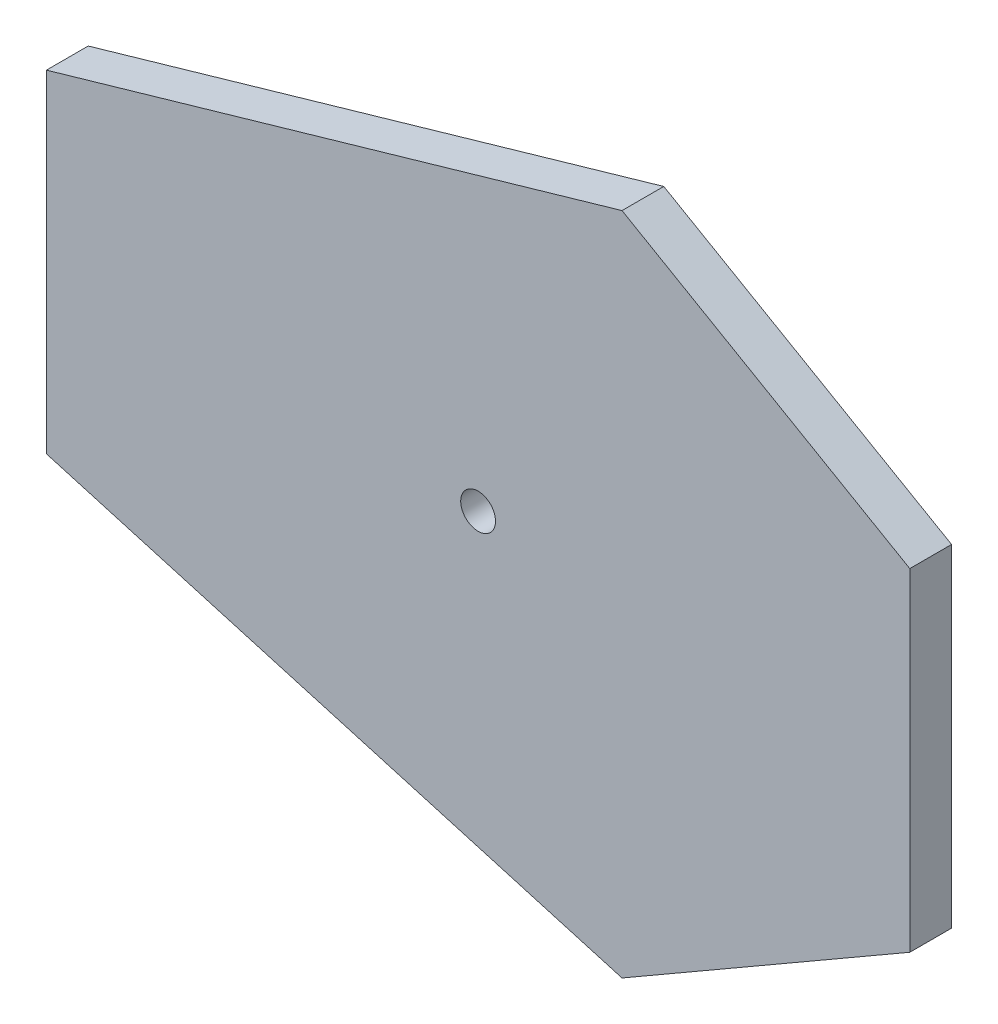
SolidWorks part; units mm, degrees
ref_plane "Front Plane" through (0, 0, 0) normal (0, 0, 1) x (1, 0, 0)
ref_plane "Top Plane" through (0, 0, 0) normal (0, 1, 0) x (1, 0, 0)
ref_plane "Right Plane" through (0, 0, 0) normal (1, 0, 0) x (0, 0, -1)
sketch "Sketch1" plane through (0, 0, 0) normal (0, 0, 1) x (1, 0, 0)
  line L0 (-36.15, 11.9319) -> (-36.15, -11.9319) construction
  line L1 (5.1833, -23.8638) -> (-36.15, -11.9319) construction
  line L2 (5.1833, -23.8638) -> (25.85, -11.9319) construction
  line L3 (25.85, -11.9319) -> (25.85, 11.9319) construction
  line L4 (25.85, 11.9319) -> (5.1833, 23.8638) construction
  line L5 (-36.15, 11.9319) -> (5.1833, 23.8638) construction
  line L6 (-36.15, 11.9319) -> (-36.15, -11.9319)
  line L7 (5.1833, -23.8638) -> (-36.15, -11.9319)
  line L8 (5.1833, -23.8638) -> (25.85, -11.9319)
  line L9 (25.85, -11.9319) -> (25.85, 11.9319)
  line L10 (25.85, 11.9319) -> (5.1833, 23.8638)
  line L11 (-36.15, 11.9319) -> (5.1833, 23.8638)
  circle A0 centre (-5.15, 0) radius 1.25
  point P7 (0, 0)
  point P8 (0, 0)
  dimension "D1" = 2.5
extrude "Boss-Extrude1" add sketch "Sketch1" along normal blind 3
